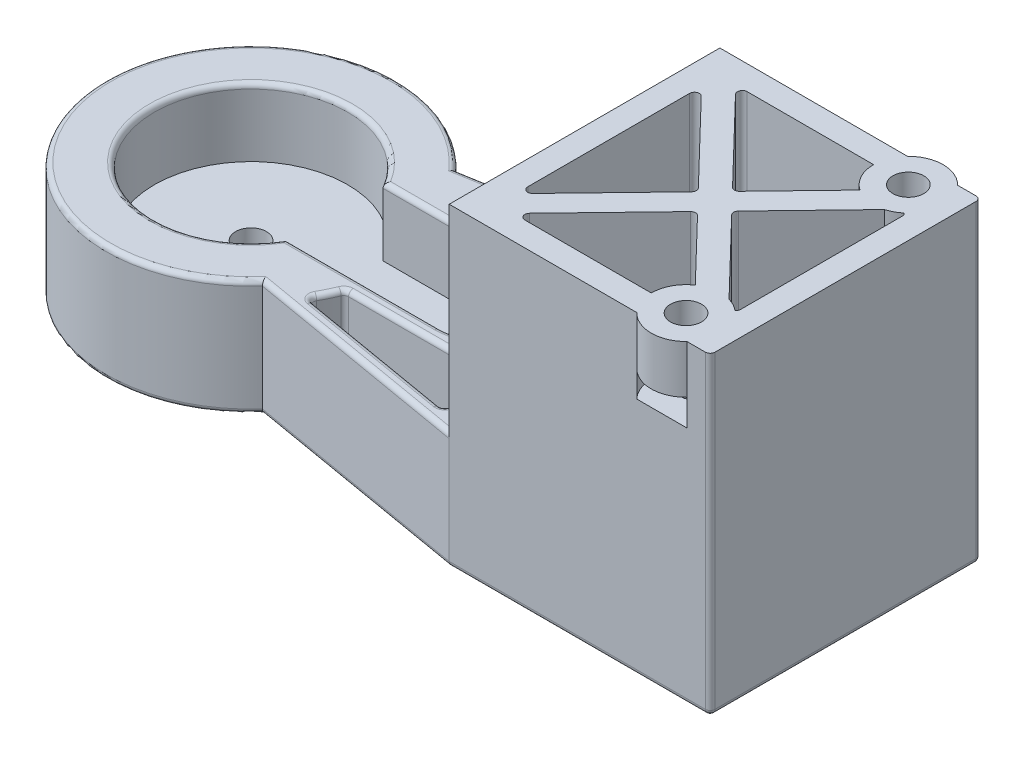
SolidWorks part; units mm, degrees
ref_plane "Front Plane" through (0, 0, 0) normal (0, 0, 1) x (1, 0, 0)
ref_plane "Top Plane" through (0, 0, 0) normal (0, 1, 0) x (1, 0, 0)
ref_plane "Right Plane" through (0, 0, 0) normal (1, 0, 0) x (0, 0, -1)
sketch "Sketch1" plane through (0, 0, 0) normal (0, 1, 0) x (1, 0, 0)
  line L0 (11.1803, 10) -> (61.5, 10)
  line L1 (11.1803, -10) -> (61.5, -10)
  line L2 (61.5, 10) -> (61.5, -10)
  arc A2 (11.1803, 10) -> (11.1803, -10) centre (0, 0) ccw
  point P6 (0, 0)
  point P8 (0, 0)
  point P10 (0, 0)
  dimension "D1" = 20
  dimension "D2" = 15
  dimension "D3" = 61.5
extrude "Boss-Extrude1" add sketch "Sketch1" along normal blind 12
sketch "Sketch2" plane through (0, 12, 0) normal (0, 1, 0) x (1, 0, 0)
  line L0 (8.6603, 5) -> (24.5, 5)
  line L1 (8.6603, -5) -> (24.5, -5)
  arc A0 (8.6603, 5) -> (8.6603, -5) centre (0, 0) ccw
  arc A1 (24.5, 5) -> (24.5, -5) centre (24.5, 0) cw
  point P7 (0, 0)
  point P8 (0, 0)
  point P9 (25.0874, 0)
  point P10 (0, 0)
  dimension "D1" = 5
  dimension "D3" = 10
  dimension "D2" = 10
  dimension "D4" = 24.5
extrude "Cut-Extrude1" cut sketch "Sketch2" against normal blind 7 contours L0 A1 L1 A0
sketch "Sketch3" plane through (0, 0, 0) normal (0, -1, 0) x (1, 0, 0)
  line L1 (34.5, -14) -> (61.5, -14)
  line L2 (34.5, -14) -> (34.5, 14)
  line L3 (34.5, 14) -> (61.5, 14)
  line L4 (61.5, -14) -> (61.5, 14)
  line L5 (34.5, -14) -> (61.5, 14) construction
  line L6 (34.5, 14) -> (61.5, -14) construction
  point P0 (48, 0)
  point P5 (0, 0)
  point P6 (0, 0)
  dimension "D1" = 27
  dimension "D2" = 28
extrude "Boss-Extrude2" add sketch "Sketch3" against normal blind 32.5
sketch "Sketch4" plane through (0, 32.5, 0) normal (0, 1, 0) x (1, 0, 0)
  line L0 (34.5, 14) -> (61.5, -14) construction
  line L1 (61.5, 14) -> (34.5, -14) construction
  line L2 (48, 14) -> (48, -14) construction
  line L3 (34.5, 14) -> (61.5, 14) construction
  line L4 (61.5, -14) -> (34.5, -14) construction
  line L5 (34.5, 0) -> (61.5, 0) construction
  line L6 (34.5, -14) -> (34.5, 14) construction
  line L7 (61.5, 14) -> (61.5, -14) construction
  line L8 (37, -9.6066) -> (37, 9.6066)
  line L9 (37, 9.6066) -> (46.2635, 0)
  line L10 (38.6472, 11.5) -> (48, 1.8008)
  line L12 (57.3528, 11.5) -> (38.6472, 11.5)
  line L13 (37, -9.6066) -> (46.2635, 0)
  line L14 (57.3528, -11.5) -> (38.6472, -11.5)
  line L15 (38.6472, -11.5) -> (48, -1.8008)
  line L16 (57.3528, 11.5) -> (48, 1.8008)
  line L17 (59, 9.6066) -> (49.7365, 0)
  line L18 (59, -9.6066) -> (59, 9.6066)
  line L19 (59, -9.6066) -> (49.7365, 0)
  line L20 (57.3528, -11.5) -> (48, -1.8008)
  point P22 (48, 1.9851)
  point P27 (48, 11.2959)
  point P29 (37, 0)
  point P33 (48, 11.5)
  point P37 (48, -11.5)
  dimension "D1" = 2.5
  dimension "D2" = 1.25
  dimension "D3" = 1.25
  dimension "D4" = 2.5
extrude "Cut-Extrude2" cut sketch "Sketch4" against normal through all
sketch "Sketch6" plane through (0, 0, 0) normal (0, 1, 0) x (1, 0, 0)
  line L0 (61.5, 0) -> (56.5, 0) construction
  line L2 (56.5, -11.5) -> (56.5, 11.5) construction
  line L3 (61.5, 14) -> (61.5, -14) construction
  circle A0 centre (56.5, -11.5) radius 3.6
  circle A1 centre (56.5, 11.5) radius 3.6
  point P6 (66.5, 0)
  point P10 (56.5, 0)
  point P11 (66.5, 0)
  point P12 (50.7373, 0)
  point P14 (61.5, 0)
  dimension "D1" = 23
  dimension "D3" = 7.2
  dimension "D2" = 5
extrude "Boss-Extrude3" add sketch "Sketch6" against normal blind 7.5 from surface starting at face at (55.9122, 32.5, 0)
sketch "Sketch7" plane through (0, 25, 0) normal (0, -1, 0) x (1, 0, 0)
  circle A0 centre (56.5, -11.5) radius 3.6
  circle A1 centre (56.5, 11.5) radius 3.6
  arc A2 (57.4875, 8.0381) -> (59, 8.9096) centre (56.5, 11.5) ccw construction
  arc A3 (54.4796, -8.5204) -> (52.9, -11.5) centre (56.5, -11.5) ccw construction
  arc A4 (52.9, 11.5) -> (54.4796, 8.5204) centre (56.5, 11.5) ccw construction
extrude "Cut-Extrude3" cut sketch "Sketch7" against normal blind 2.5 and the other way blind 0.25
sketch "Sketch8" plane through (0, 32.5, 0) normal (0, 1, 0) x (1, 0, 0)
  circle A0 centre (56.5, 11.5) radius 1.6
  circle A1 centre (56.5, -11.5) radius 1.6
  arc A2 (59.0904, 14) -> (53.9096, 14) centre (56.5, 11.5) ccw construction
  arc A3 (53.9096, -14) -> (59.0904, -14) centre (56.5, -11.5) ccw construction
  dimension "D1" = 3.2
extrude "Cut-Extrude4" cut sketch "Sketch8" against normal up to next
sketch "Sketch11" plane through (0, 12, 0) normal (0, 1, 0) x (1, 0, 0)
  line L0 (34.5, -14) -> (11.1803, -10)
  line L1 (11.1803, -10) -> (34.5, -10)
  line L2 (34.5, -10) -> (34.5, -14)
  line L3 (11.1803, 10) -> (34.5, 14)
  line L4 (34.5, 14) -> (34.5, 10)
  line L5 (34.5, 10) -> (11.1803, 10)
extrude "Boss-Extrude4" add sketch "Sketch11" against normal up to surface (12 mm away) up to face at (55.9122, 0, 0)
sketch "Sketch12" plane through (0, 12, 0) normal (0, 1, 0) x (1, 0, 0)
  line L0 (11.1803, -10) -> (34.5, -14) construction
  line L1 (14.9345, 9.122) -> (32, 12.0493)
  line L2 (32, 12.0493) -> (32, 6.5)
  line L3 (32, 6.5) -> (16.2481, 6.5)
  line L4 (16.2481, -6.5) -> (32, -6.5)
  line L5 (32, -6.5) -> (32, -12.0493)
  line L6 (32, -12.0493) -> (14.9345, -9.122)
  line L7 (34.5, 14) -> (11.1803, 10) construction
  line L8 (34.5, -14) -> (34.5, 14) construction
  line L9 (8.6603, -5) -> (24.5, -5) construction
  line L10 (8.6603, 5) -> (24.5, 5) construction
  line L11 (34.5, 14) -> (34.5, -14) construction
  circle A0 centre (0, 0) radius 15 construction
  arc A1 (14.9345, 9.122) -> (16.2481, 6.5) centre (0, 0) cw
  arc A2 (14.9345, -9.122) -> (16.2481, -6.5) centre (0, 0) ccw
  dimension "D1" = 2.5
  dimension "D2" = 2.5
  dimension "D3" = 2.5
  dimension "D4" = 1.5
  dimension "D5" = 1.5
  dimension "D6" = 1.5
  dimension "D7" = 2.5
  dimension "D8" = 1.5
extrude "Cut-Extrude5" cut sketch "Sketch12" against normal up to next
sketch "Sketch13" plane through (0, 5, 0) normal (0, 1, 0) x (1, 0, 0)
  circle A0 centre (0, 0) radius 1.6
  circle A1 centre (24.5, 0) radius 1.6
  point P5 (0, 0)
  point P6 (0, 0)
  dimension "D1" = 3.2
  dimension "D2" = 3.2
  dimension "D3" = 24.5
extrude "Cut-Extrude6" cut sketch "Sketch13" against normal up to next
sketch "Sketch14" plane through (0, 0, 0) normal (0, -1, 0) x (1, 0, 0)
  circle A0 centre (0, 0) radius 2.85
  circle A1 centre (24.5, 0) radius 2.85
  circle A2 centre (24.5, 0) radius 1.6 construction
  circle A3 centre (0, 0) radius 1.6 construction
  point P4 (0, 0)
  dimension "D1" = 5.7
  dimension "D2" = 5.7
extrude "Cut-Extrude7" cut sketch "Sketch14" against normal blind 3.2
fillet "Fillet1" radius 0.5 64 edges at (48, 0, 11.5) (37, 16.25, 9.6066) (38.6472, 16.25, 11.5) (57.3528, 12.375, 11.5) (59, 12.375, 9.6066) (59, 12.375, -9.6066) (57.3528, 12.375, -11.5) (38.6472, 16.25, -11.5) (37, 16.25, -9.6066) (46.2635, 16.25, 0) (49.7365, 16.25, 0) (48, 16.25, -1.8008) (48, 16.25, 1.8008) (52.6764, 0, 6.6504) (43.3236, 0, 6.6504) (41.6318, 0, 4.8033) (41.6318, 0, -4.8033) (37, 0, 0) (43.3236, 0, -6.6504) (48, 0, -11.5) (52.6764, 0, -6.6504) (54.3682, 0, -4.8033) (59, 0, 0) (54.3682, 0, 4.8033) (-15, 0, 0) (22.8402, 12, -12) (-15, 12, 0) (22.8402, 12, 12) (22.8402, 0, 12) (48, 0, 14) (22.8402, 0, -12) (48, 0, -14) (61.5, 0, 0) (61.5, 16.25, 14) (61.5, 16.25, -14) (16.5801, 12, -5) (29.5, 12, 0) (32, 0, -9.2746) (23.4672, 0, -10.5857) (15.6463, 0, -7.8386) (24.124, 0, -6.5) (32, 0, 9.2746) (23.4672, 0, 10.5857) (24.124, 0, 6.5) (15.6463, 0, 7.8386) (16.5801, 12, 5) (-10, 12, 0) (32, 12, 9.2746) (24.124, 12, 6.5) (23.4672, 12, 10.5857) (15.6463, 12, 7.8386) (15.6463, 12, -7.8386) (23.4672, 12, -10.5857) (24.124, 12, -6.5) (32, 12, -9.2746) (52.9, 26.125, 11.5) (32, 6, 6.5) (32, 6, 12.0493) (16.2481, 6, 6.5) (14.9345, 6, 9.122) (14.9345, 6, -9.122) (16.2481, 6, -6.5) (32, 6, -12.0493) (32, 6, -6.5)
